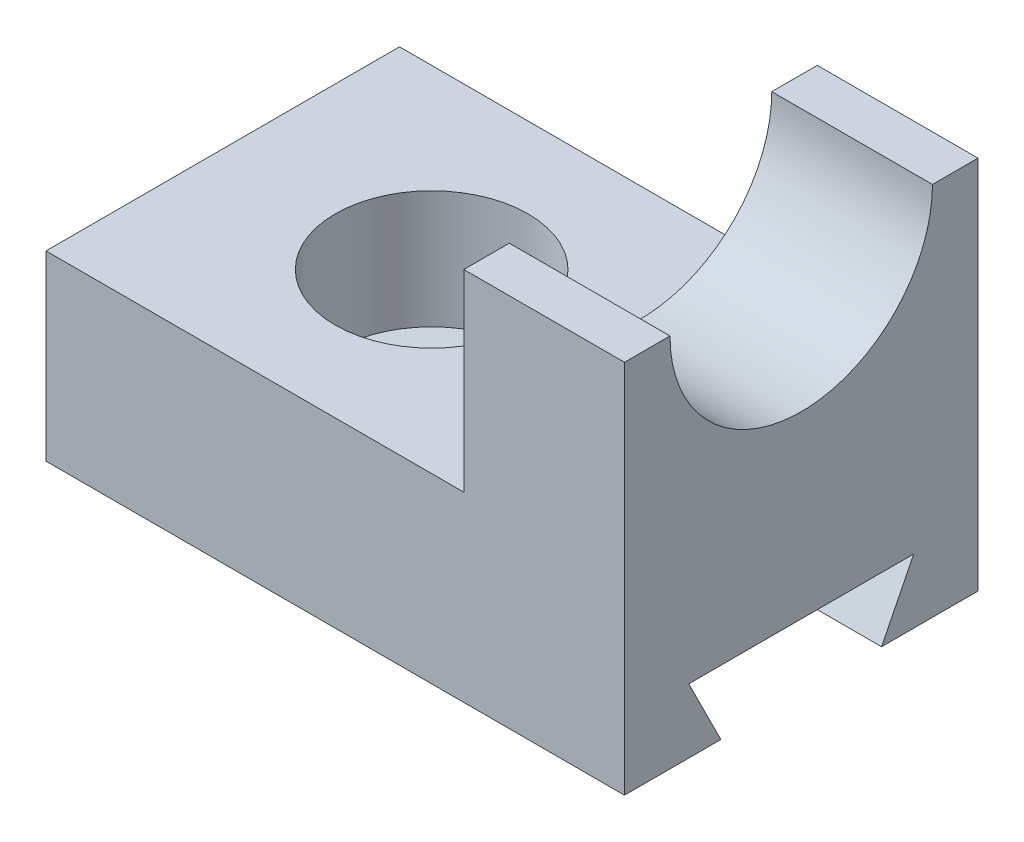
SolidWorks part; units mm, degrees
ref_plane "前视基准面" through (0, 0, 0) normal (0, 0, 1) x (1, 0, 0)
ref_plane "上视基准面" through (0, 0, 0) normal (0, 1, 0) x (1, 0, 0)
ref_plane "右视基准面" through (0, 0, 0) normal (1, 0, 0) x (0, 0, -1)
other "Configuration Table"
sketch "草图1" plane through (0, 0, 0) normal (0, 1, 0) x (1, 0, 0)
  line L0 (24, 33) -> (24, -33)
  line L1 (-54, 33) -> (54, 33)
  line L2 (-54, 33) -> (-54, -33)
  line L3 (-54, -33) -> (54, -33)
  line L4 (54, 33) -> (54, -33)
  line L5 (-54, 33) -> (54, -33) construction
  line L6 (-54, -33) -> (54, 33) construction
  point P0 (0, 0)
  point P8 (40.6904, -33)
  dimension "D1" = 108
  dimension "D2" = 66
  dimension "D3" = 30
extrude "凸台-拉伸1" add sketch "草图1" along normal blind 34 contours L2 L3 L0 L1 region at (-15, 0, 0)
extrude "凸台-拉伸2" add sketch "草图1<3>" along normal blind 70 contours L4 L1 L0 L3 region at (39, 0, 0)
sketch "草图1<3>" plane through (0, 0, 0) normal (0, 1, 0) x (1, 0, 0) same geometry as "草图1"
sketch "草图2" plane through (0, 34, 0) normal (0, 1, 0) x (1, 0, 0)
  line L0 (-15, 33) -> (-15, -33) construction
  line L1 (-54, 33) -> (24, 33) construction
  line L2 (-54, -33) -> (24, -33) construction
  line L3 (-54, 0) -> (24, 0) construction
  line L4 (-54, 33) -> (-54, -33) construction
  line L5 (24, 33) -> (24, -33) construction
  circle A0 centre (-15, 0) radius 18
  dimension "D1" = 36
extrude "切除-拉伸1" cut sketch "草图2" against normal blind 23
sketch "草图3" plane through (24, 0, 0) normal (-1, 0, 0) x (0, 0, 1)
  line L0 (0, 70) -> (0, 34) construction
  line L1 (-33, 70) -> (33, 70) construction
  line L2 (-33, 34) -> (33, 34) construction
  circle A0 centre (0, 70) radius 24.5
  dimension "D1" = 49
extrude "切除-拉伸2" cut sketch "草图3" against normal blind 70
sketch "草图4" plane through (-54, 0, 0) normal (-1, 0, 0) x (0, 0, 1)
  line L0 (0, 0) -> (0, 24.0058) construction
  line L1 (21, 12) -> (-21, 12)
  line L2 (-21, 12) -> (-15, 0)
  line L3 (-33, 0) -> (33, 0) construction
  line L4 (-15, 0) -> (15, 0)
  line L5 (21, 12) -> (15, 0)
  point P10 (-18.5534, 10.6678)
  point P11 (0, 12)
  dimension "D1" = 30
  dimension "D2" = 12
  dimension "D3" = 42
extrude "切除-拉伸3" cut sketch "草图4" against normal up to next
